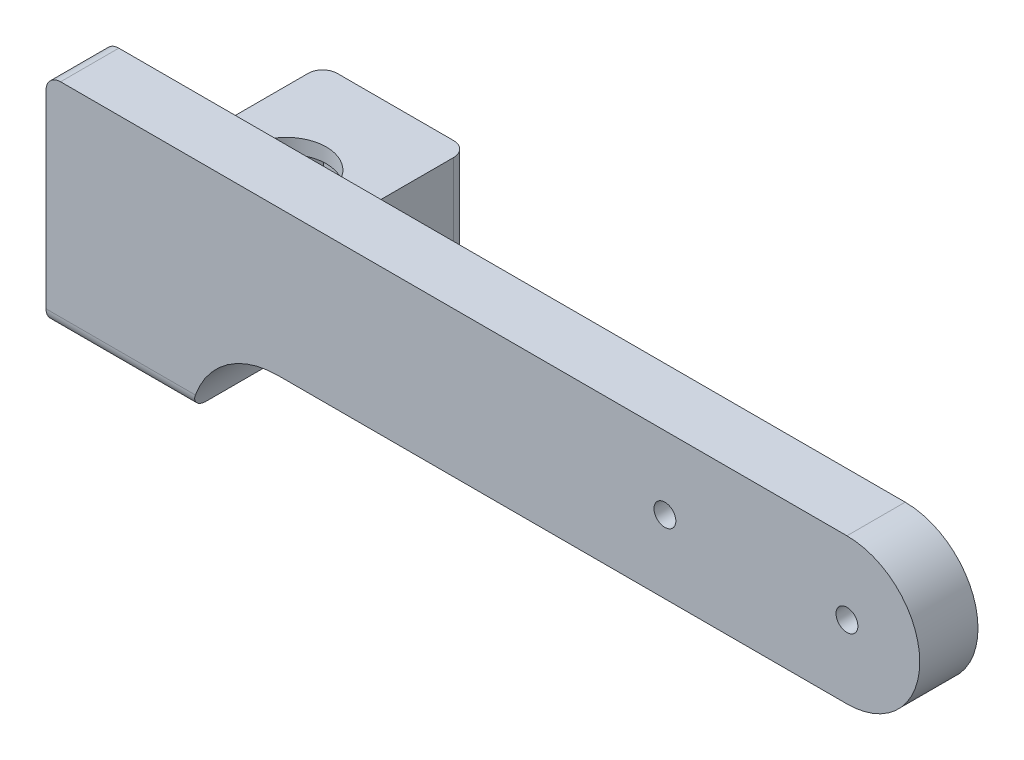
SolidWorks part; units mm, degrees
ref_plane "Front Plane" through (0, 0, 0) normal (0, 0, 1) x (1, 0, 0)
ref_plane "Top Plane" through (0, 0, 0) normal (0, 1, 0) x (1, 0, 0)
ref_plane "Right Plane" through (0, 0, 0) normal (1, 0, 0) x (0, 0, -1)
sketch "Sketch1" plane through (0, 0, 0) normal (0, 0, 1) x (1, 0, 0)
  line L1 (-25, 10) -> (85, 10)
  line L2 (-25, 10) -> (-25, -10)
  line L3 (-25, -10) -> (85, -10)
  arc A0 (85, -10) -> (85, 10) centre (85, 0) ccw
  dimension "D5" = 20
  dimension "D1" = 20
  dimension "D2" = 10
  dimension "D3" = 110
  dimension "D4" = 25
extrude "Boss-Extrude1" add sketch "Sketch1" along normal blind 8
sketch "Sketch2" plane through (0, 0, 8) normal (0, 0, 1) x (1, 0, 0)
  line L0 (85, 10) -> (-25, 10) construction
  circle A1 centre (85, 0) radius 1.5
  dimension "D2" = 3
  dimension "D1" = 10
  dimension "D3" = 85
extrude "Cut-Extrude1" cut sketch "Sketch2" against normal blind 10
sketch "Sketch6" plane through (0, 0, 0) normal (0, 0, -1) x (-1, 0, 0)
  line L1 (25, -10) -> (5, -10)
  line L2 (25, -10) -> (25, -20)
  line L3 (25, -20) -> (5, -20)
  line L4 (5, -10) -> (5, -20)
  dimension "D1" = 20
  dimension "D2" = 10
extrude "Boss-Extrude3" add sketch "Sketch6" along normal blind 30 and the other way blind 8
fillet "Fillet3" radius 12 1 edges at (-5, -10, 4)
sketch "Sketch7" plane through (0, -10, 0) normal (0, 1, 0) x (1, 0, 0)
  line L1 (-5, 30) -> (-25, 30)
  line L2 (-5, 30) -> (-5, 0)
  line L3 (-5, 0) -> (-25, 0)
  line L4 (-25, 30) -> (-25, 0)
extrude "Boss-Extrude4" add sketch "Sketch7" along normal blind 2
sketch "Sketch8" plane through (0, -20, 0) normal (0, -1, 0) x (1, 0, 0)
  line L1 (-5, 8) -> (-25, 8) construction
  line L2 (-5, 0) -> (-5, -30) construction
  line L4 (-12.0928, -7.0126) -> (-20.4637, -8.4886)
  line L15 (-20.4637, -8.4886) -> (-23.3709, -16.476)
  line L16 (-23.3709, -16.476) -> (-17.9072, -22.9874)
  line L17 (-17.9072, -22.9874) -> (-9.5363, -21.5114)
  line L18 (-9.5363, -21.5114) -> (-6.6291, -13.524)
  line L19 (-6.6291, -13.524) -> (-12.0928, -7.0126)
  dimension "D2" = 8.5
  dimension "D3" = 1.6291
  dimension "D1" = 15.0126
extrude "Cut-Extrude3" cut sketch "Sketch8" against normal blind 10
sketch "Sketch9" plane through (0, -10, 0) normal (0, -1, 0) x (1, 0, 0)
  line L0 (-20.4637, -8.4886) -> (-9.5363, -21.5114) construction
  line L1 (-12.0928, -7.0126) -> (-17.9072, -22.9874) construction
  line L2 (16.927, -11) -> (16.927, -10.0428) construction
  circle A0 centre (-15, -15) radius 5.5
  dimension "D1" = 11
extrude "Cut-Extrude4" cut sketch "Sketch9" against normal blind 10
fillet "Fillet4" radius 5 2 edges at (-5, -14, 0) (-15, -8, 0)
fillet "Fillet5" radius 2 4 edges at (-15, -20, 8) (-25, 10, 4) (-5, -14, -30) (-25, -14, -30)
sketch "Sketch10" plane through (0, 0, 8) normal (0, 0, 1) x (1, 0, 0)
  line L0 (0, 0) -> (0, -23.8861) construction
  line L1 (0, 0) -> (23.1203, 0) construction
  circle A1 centre (60, 0) radius 1.5
  dimension "D2" = 3
  dimension "D1" = 60
extrude "Cut-Extrude5" cut sketch "Sketch10" against normal blind 10
